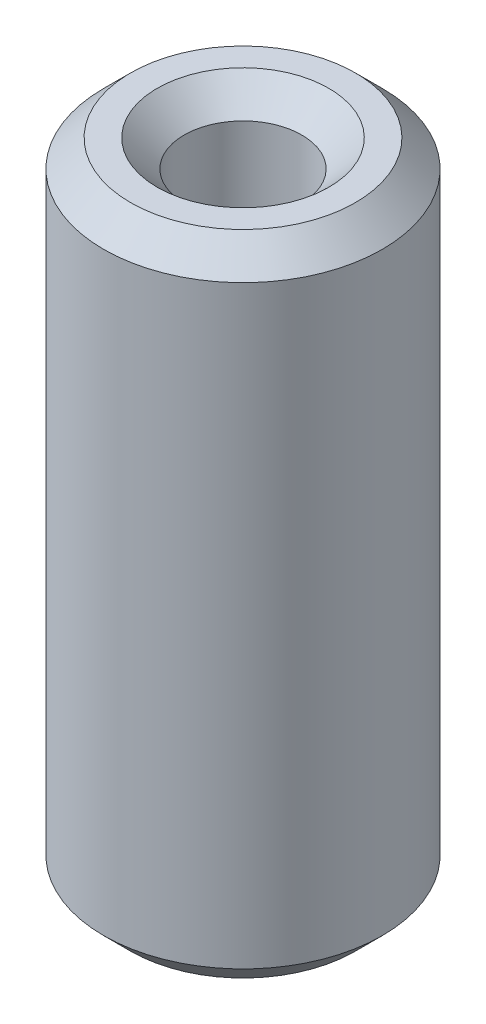
SolidWorks part; units mm, degrees
ref_plane "Front Plane" through (0, 0, 0) normal (0, 0, 1) x (1, 0, 0)
ref_plane "Top Plane" through (0, 0, 0) normal (0, 1, 0) x (1, 0, 0)
ref_plane "Right Plane" through (0, 0, 0) normal (1, 0, 0) x (0, 0, -1)
sketch "Sketch1" plane through (0, 0, 0) normal (0, 1, 0) x (1, 0, 0)
  circle A0 centre (0, 0) radius 7.5
  dimension "SLEEVE_OD" = 15
extrude "Boss-Extrude1" add sketch "Sketch1" along normal blind 34.8867
sketch "Sketch2" plane through (0, 0, 0) normal (0, 1, 0) x (1, 0, 0)
  circle A0 centre (0, 0) radius 3.165
  dimension "BORE_D" = 6.3301
extrude "Cut-Extrude1" cut sketch "Sketch2" along normal through all
chamfer "Chamfer1" distance 1.4514 angle 45 4 edges at (0, 34.8867, 3.165) (0, 0, 3.165) (0, 0, 7.5) (0, 34.8867, 7.5)
